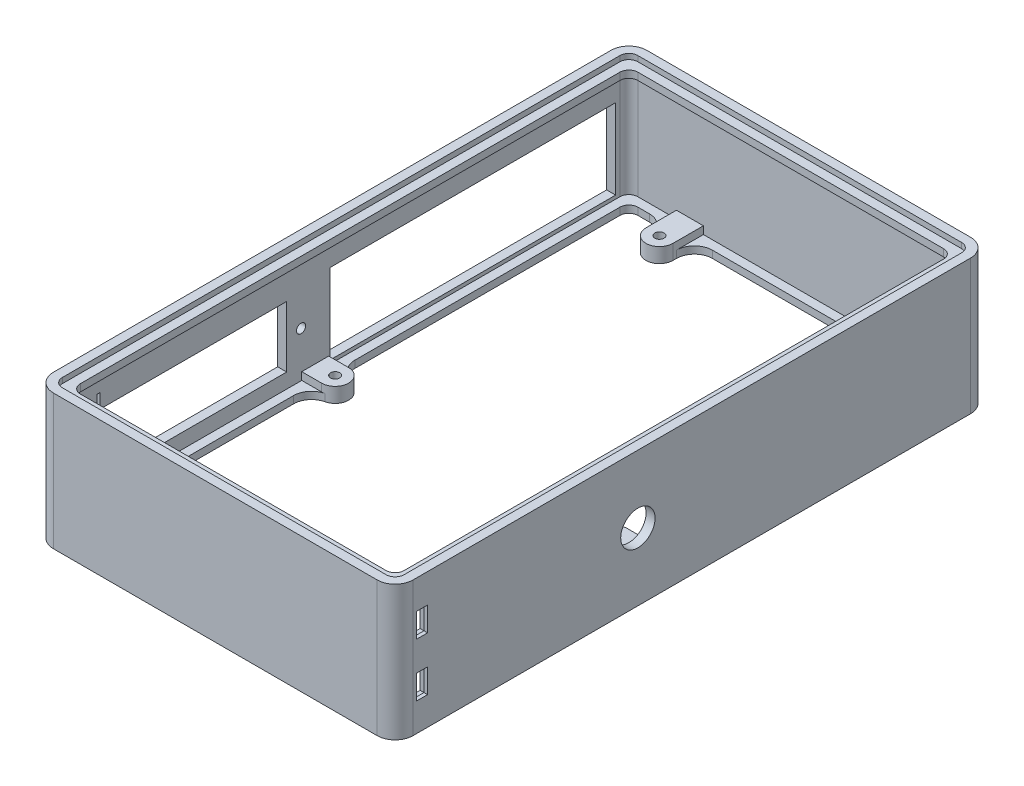
SolidWorks part; units mm, degrees
ref_plane "Front Plane" through (0, 0, 0) normal (0, 0, 1) x (1, 0, 0)
ref_plane "Top Plane" through (0, 0, 0) normal (0, 1, 0) x (1, 0, 0)
ref_plane "Right Plane" through (0, 0, 0) normal (1, 0, 0) x (0, 0, -1)
sketch "Sketch1" plane through (0, 0, 0) normal (0, 1, 0) x (1, 0, 0)
  line L1 (0, 0) -> (200, 0)
  line L2 (0, 0) -> (0, 330)
  line L3 (0, 330) -> (200, 330)
  line L4 (200, 0) -> (200, 330)
extrude "Boss-Extrude1" add sketch "Sketch1" along normal blind 75
fillet "Fillet1" radius 10 4 edges at (0, 37.5, -330) (200, 37.5, -330) (0, 37.5, 0) (200, 37.5, 0)
sketch "Sketch2" plane through (0, 75, 0) normal (0, 1, 0) x (1, 0, 0)
  line L8 (190, 325) -> (10, 325)
  line L9 (5, 320) -> (5, 10)
  line L10 (10, 5) -> (190, 5)
  line L11 (195, 10) -> (195, 320)
  line L12 (190, 325) -> (10, 325)
  line L13 (5, 320) -> (5, 10)
  line L14 (10, 5) -> (190, 5)
  line L15 (195, 10) -> (195, 320)
  arc A8 (10, 325) -> (5, 320) centre (10, 320) ccw
  arc A9 (5, 10) -> (10, 5) centre (10, 10) ccw
  arc A10 (190, 5) -> (195, 10) centre (190, 10) ccw
  arc A11 (195, 320) -> (190, 325) centre (190, 320) ccw
  arc A12 (10, 325) -> (5, 320) centre (10, 320) ccw
  arc A13 (5, 10) -> (10, 5) centre (10, 10) ccw
  arc A14 (190, 5) -> (195, 10) centre (190, 10) ccw
  arc A15 (195, 320) -> (190, 325) centre (190, 320) ccw
  dimension "D1" = 5
extrude "Cut-Extrude1" cut sketch "Sketch2" against normal blind 75
ref_plane "Plane1" through (0, 72, 0) normal (0, 1, 0) x (1, 0, 0)
ref_plane "Plane2" through (0, 3, 0) normal (0, -1, 0) x (-1, 0, 0)
sketch "Sketch3" plane through (0, 72, 0) normal (0, 1, 0) x (1, 0, 0)
  line L0 (10, 5) -> (190, 5) construction
  line L1 (195, 10) -> (195, 320) construction
  line L2 (5, 320) -> (5, 10) construction
  line L3 (190, 325) -> (10, 325) construction
  line L4 (10, 5) -> (190, 5)
  line L5 (195, 10) -> (195, 320)
  line L6 (5, 320) -> (5, 10)
  line L7 (190, 325) -> (10, 325)
  line L8 (10, 10) -> (190, 10)
  line L9 (190, 10) -> (190, 320)
  line L10 (190, 320) -> (10, 320)
  line L11 (10, 320) -> (10, 10)
  arc A0 (5, 10) -> (10, 5) centre (10, 10) ccw construction
  arc A1 (190, 5) -> (195, 10) centre (190, 10) ccw construction
  arc A2 (195, 320) -> (190, 325) centre (190, 320) ccw construction
  arc A3 (10, 325) -> (5, 320) centre (10, 320) ccw construction
  arc A4 (5, 10) -> (10, 5) centre (10, 10) ccw
  arc A5 (190, 5) -> (195, 10) centre (190, 10) ccw
  arc A6 (195, 320) -> (190, 325) centre (190, 320) ccw
  arc A7 (10, 325) -> (5, 320) centre (10, 320) ccw
  arc A8 (10, 10) -> (10, 10) centre (10, 10) ccw
  arc A9 (190, 10) -> (190, 10) centre (190, 10) ccw
  arc A10 (190, 320) -> (190, 320) centre (190, 320) ccw
  arc A11 (10, 320) -> (10, 320) centre (10, 320) ccw
  dimension "D1" = 5
extrude "Boss-Extrude2" add sketch "Sketch3" against normal blind 4
sketch "Sketch4" plane through (0, 3, 0) normal (0, -1, 0) x (-1, 0, 0)
  line L0 (-190, 320) -> (-190, 10)
  line L1 (-190, 10) -> (-10, 10)
  line L2 (-10, 10) -> (-10, 320)
  line L3 (-10, 320) -> (-190, 320)
  line L4 (-5, 10) -> (-5, 320)
  line L5 (-10, 325) -> (-190, 325)
  line L6 (-195, 320) -> (-195, 10)
  line L7 (-190, 5) -> (-10, 5)
  line L8 (-5, 10) -> (-5, 320)
  line L9 (-10, 325) -> (-190, 325)
  line L10 (-195, 320) -> (-195, 10)
  line L11 (-190, 5) -> (-10, 5)
  arc A0 (-190, 10) -> (-190, 10) centre (-190, 10) ccw
  arc A1 (-10, 10) -> (-10, 10) centre (-10, 10) ccw
  arc A2 (-10, 320) -> (-10, 320) centre (-10, 320) ccw
  arc A3 (-190, 320) -> (-190, 320) centre (-190, 320) ccw
  arc A4 (-10, 5) -> (-5, 10) centre (-10, 10) ccw
  arc A5 (-5, 320) -> (-10, 325) centre (-10, 320) ccw
  arc A6 (-190, 325) -> (-195, 320) centre (-190, 320) ccw
  arc A7 (-195, 10) -> (-190, 5) centre (-190, 10) ccw
  arc A8 (-10, 5) -> (-5, 10) centre (-10, 10) ccw
  arc A9 (-5, 320) -> (-10, 325) centre (-10, 320) ccw
  arc A10 (-190, 325) -> (-195, 320) centre (-190, 320) ccw
  arc A11 (-195, 10) -> (-190, 5) centre (-190, 10) ccw
  dimension "D1" = 0
  dimension "D2" = 5
extrude "Boss-Extrude3" add sketch "Sketch4" against normal blind 4
sketch "Sketch8" plane through (5, 0, 0) normal (1, 0, 0) x (0, 0, -1)
  line L0 (320, 7) -> (317.62, 7)
  line L1 (10, 7) -> (320, 7) construction
  line L2 (317.62, 7) -> (317.62, 9)
  line L3 (317.62, 9) -> (317.62, 53.5)
  line L4 (317.62, 53.5) -> (158.87, 53.5)
  line L6 (158.87, 53.5) -> (317.62, 53.5)
  line L7 (158.87, 53.5) -> (158.87, 9)
  line L8 (158.87, 9) -> (317.62, 9)
  line L9 (317.62, 53.5) -> (317.62, 9)
extrude "Cut-Extrude2" cut sketch "Sketch8" against normal blind 40 contours L7 L8 L3 L4 region at (5, 31.25, -238.245)
sketch "Sketch11" plane through (0, 3, 0) normal (0, -1, 0) x (1, 0, 0)
  line L1 (16.06, -158.09) -> (10, -158.09)
  line L2 (10, -10) -> (10, -320) construction
  line L4 (10, -143.09) -> (16.06, -143.09)
  line L5 (31.42, -308.07) -> (31.42, -320)
  line L6 (10, -320) -> (190, -320) construction
  line L8 (46.42, -320) -> (46.42, -308.07)
  line L9 (171, -300.57) -> (190, -300.57)
  line L10 (190, -320) -> (190, -10) construction
  line L13 (163.5, -320) -> (163.5, -308.07)
  line L14 (171, -158.09) -> (190, -158.09)
  line L16 (190, -143.09) -> (171, -143.09)
  line L17 (190, -158.09) -> (195, -158.09)
  line L18 (195, -10) -> (195, -320) construction
  line L19 (195, -158.09) -> (195, -143.09)
  line L20 (195, -320) -> (195, -10) construction
  line L21 (195, -143.09) -> (190, -143.09)
  line L22 (190, -300.57) -> (195, -300.57)
  line L23 (195, -300.57) -> (195, -320)
  line L24 (163.5, -320) -> (163.5, -325)
  line L25 (190, -325) -> (10, -325) construction
  line L26 (163.5, -325) -> (190, -325)
  line L27 (5, -10) -> (5, -320) construction
  line L29 (46.42, -320) -> (46.42, -325)
  line L30 (46.42, -325) -> (31.42, -325)
  line L31 (31.42, -320) -> (31.42, -325)
  line L32 (10, -158.09) -> (5, -158.09)
  line L34 (10, -143.09) -> (5, -143.09)
  line L35 (5, -158.09) -> (5, -143.09)
  circle A0 centre (38.92, -308.07) radius 2.55
  circle A1 centre (171, -308.07) radius 2.55
  circle A2 centre (171, -150.59) radius 2.55
  circle A3 centre (16.06, -150.59) radius 2.55
  arc A4 (16.06, -158.09) -> (16.06, -143.09) centre (16.06, -150.59) ccw
  arc A5 (171, -143.09) -> (171, -158.09) centre (171, -150.59) ccw
  arc A6 (171, -300.57) -> (163.5, -308.07) centre (171, -308.07) ccw
  arc A7 (46.42, -308.07) -> (31.42, -308.07) centre (38.92, -308.07) ccw
  arc A8 (190, -325) -> (195, -320) centre (190, -320) ccw construction
  arc A9 (190, -325) -> (195, -320) centre (190, -320) ccw
extrude "Boss-Extrude4" add sketch "Sketch11" against normal blind 8.23
sketch "Sketch12" plane through (0, 0, 0) normal (-1, 0, 0) x (0, 0, 1)
  line L0 (-134.7, 32.25) -> (-142.7, 32.25)
  line L4 (-134.7, 15.25) -> (-32.9, 15.25)
  line L5 (-134.7, 15.25) -> (-134.7, 49.25)
  line L6 (-134.7, 49.25) -> (-32.9, 49.25)
  line L7 (-32.9, 49.25) -> (-32.9, 15.25)
  circle A0 centre (-142.7, 32.25) radius 2.55
extrude "Cut-Extrude3" cut sketch "Sketch12" against normal blind 31.23 contours L7 L6 L5 L4 | A0 region at (0, 32.25, -145.1779) region at (0, 32.25, -83.8)
sketch "Sketch13" plane through (195, 0, 0) normal (-1, 0, 0) x (0, 0, 1)
  line L0 (-10, 37.5) -> (-130, 37.5)
  line L1 (-10, 7) -> (-10, 68) construction
  line L2 (-10, 37.5) -> (-135, 37.5)
  circle A0 centre (-135, 37.5) radius 9.55
extrude "Cut-Extrude4" cut sketch "Sketch13" against normal blind 31.23
fillet "Fillet2" radius 10 4 edges at (31.42, 5, -320) (46.42, 5, -320) (10, 5, -143.09) (10, 5, -158.09)
fillet "Fillet3" radius 20 2 edges at (190, 5, -143.09) (190, 5, -158.09)
fillet "Fillet4" radius 5 7 edges at (10, 5, -10) (190, 5, -10) (10, 5, -320) (10, 70, -320) (190, 70, -320) (190, 70, -10) (10, 70, -10)
sketch "Sketch14" plane through (0, 0, 0) normal (-1, 0, 0) x (0, 0, 1)
  line L0 (-32.9, 15.25) -> (-30.9, 15.25)
  line L1 (-30.9, 15.25) -> (-30.9, 10.25)
  line L2 (-30.9, 10.25) -> (-29.15, 10.25)
  line L3 (-32.9, 49.25) -> (-30.9, 49.25)
  line L4 (-30.9, 49.25) -> (-30.9, 57.25)
  line L6 (-30.9, 57.25) -> (-29.15, 57.25)
  line L7 (-30.9, 57.25) -> (-30.9, 10.25)
  line L8 (-30.9, 10.25) -> (-29.15, 10.25)
  line L9 (-29.15, 57.25) -> (-29.15, 10.25)
extrude "Cut-Extrude5" cut sketch "Sketch14" against normal blind 10 contours L9 L6 L4 L7 L1 L2 region at (0, 33.75, -30.025)
sketch "Sketch15" plane through (0, 0, 0) normal (-1, 0, 0) x (0, 0, 1)
  line L1 (-30.9, 10.25) -> (-32.9, 10.25)
  line L2 (-30.9, 10.25) -> (-30.9, 57.2714)
  line L3 (-30.9, 57.2714) -> (-32.9, 57.2714)
  line L4 (-32.9, 10.25) -> (-32.9, 57.2714)
extrude "Boss-Extrude5" add sketch "Sketch15" along normal blind 8
sketch "Sketch16" plane through (0, 0, -32.9) normal (0, 0, -1) x (-1, 0, 0)
  line L0 (0, 15.25) -> (0.5, 15.25)
  line L1 (0.5, 15.25) -> (0.5, 31.75)
  circle A0 centre (0.5, 31.75) radius 2.55
extrude "Cut-Extrude6" cut sketch "Sketch16" against normal blind 2 contours A0 region at (-2.2521, 29.9979, -32.9)
sketch "Sketch17" plane through (0, 0, -32.9) normal (0, 0, -1) x (-1, 0, 0)
  circle A0 centre (0.5, 31.75) radius 4.5
  circle A1 centre (0.5, 31.75) radius 2.55
extrude "Boss-Extrude6" add sketch "Sketch17" along normal blind 3
chamfer "Chamfer1" distance 3 angle 45 1 edges at (-5, 31.75, -32.9)
fillet "Fillet5" radius 5 2 edges at (-8, 57.2714, -31.9) (-8, 10.25, -31.9)
chamfer "Chamfer2" distance 3 angle 45 2 edges at (0, 53.2607, -32.9) (0, 12.75, -32.9)
sketch "Sketch19" plane through (200, 0, 0) normal (1, 0, 0) x (0, 0, -1)
  line L0 (5, 7) -> (5, 68) construction
  line L1 (5, 7) -> (5, 68)
  line L2 (5, 37.5) -> (25, 37.5)
  line L3 (15, 37.5) -> (15, 52)
  line L4 (15, 52) -> (15, 22.25)
  line L5 (15, 52) -> (15, 44.75)
  line L6 (15, 44.75) -> (18.5, 44.75)
  line L7 (15, 22.25) -> (15, 29.5)
  line L8 (18.5, 44.75) -> (11.5, 44.75)
  line L9 (18.5, 44.75) -> (18.5, 59.25)
  line L10 (18.5, 59.25) -> (11.5, 59.25)
  line L11 (11.5, 44.75) -> (11.5, 59.25)
  line L12 (15, 29.5) -> (18.5, 29.5)
  line L14 (18.5, 29.5) -> (11.5, 29.5)
  line L15 (18.5, 29.5) -> (18.5, 15)
  line L16 (18.5, 15) -> (11.5, 15)
  line L17 (11.5, 29.5) -> (11.5, 15)
extrude "Cut-Extrude8" cut sketch "Sketch19" against normal blind 18 contours L11 L8 L6 L9 L10 | L14 L17 L16 L15 L12 region at (200, 44.911, -13.25) region at (200, 29.339, -16.75)
sketch "Sketch20" plane through (0, 0, -5) normal (0, 0, -1) x (-1, 0, 0)
  line L0 (-195, 29.5) -> (-195, 15) construction
  line L1 (-195, 29.5) -> (-195, 15)
  line L2 (-195, 20.2001) -> (-188, 20.2001)
  line L3 (-188, 20.2001) -> (-185, 20.2001)
  line L4 (-195, 44.75) -> (-195, 59.25) construction
  line L5 (-195, 44.75) -> (-195, 59.25)
  line L6 (-195, 29.5) -> (-195, 15)
  line L7 (-195, 29.5) -> (-195, 44.75)
  line L8 (-195, 15) -> (-185, 15)
  line L9 (-185, 37.125) -> (-185, 62.125)
  line L10 (-180, 37.125) -> (-178, 37.125)
  line L11 (-185, 37.125) -> (-185, 12.125)
  line L12 (-185, 12.125) -> (-170, 12.125)
  line L13 (-185, 59.25) -> (-170, 59.25)
  line L14 (-185, 62.125) -> (-170, 62.125)
  circle A0 centre (-178, 37.125) radius 2.55
  circle A1 centre (-168, 62.125) radius 2.55
  circle A2 centre (-168, 12.125) radius 2.55
sketch "Sketch22" plane through (200, 0, 0) normal (1, 0, 0) x (0, 0, -1)
  line L0 (11.5, 44.75) -> (11.5, 59.25) construction
  line L1 (18.5, 59.25) -> (11.5, 59.25)
  line L2 (18.5, 59.25) -> (18.5, 59.625)
  line L3 (18.5, 59.625) -> (11.5, 59.625)
  line L4 (11.5, 59.25) -> (11.5, 59.625)
  line L5 (11.5, 29.5) -> (11.5, 15) construction
  line L6 (18.5, 29.5) -> (11.5, 29.5)
  line L7 (18.5, 29.5) -> (18.5, 29.875)
  line L8 (18.5, 29.875) -> (11.5, 29.875)
  line L9 (11.5, 29.5) -> (11.5, 29.875)
extrude "Cut-Extrude9" cut sketch "Sketch22" against normal blind 18
sketch "Sketch23" plane through (200, 0, 0) normal (1, 0, 0) x (0, 0, -1)
  line L0 (11.5, 44.75) -> (11.5, 59.625) construction
  line L1 (18.5, 44.75) -> (11.5, 44.75)
  line L2 (18.5, 44.75) -> (18.5, 45.125)
  line L3 (18.5, 45.125) -> (11.5, 45.125)
  line L4 (11.5, 44.75) -> (11.5, 45.125)
  line L5 (11.5, 29.875) -> (11.5, 15) construction
  line L6 (18.5, 15) -> (11.5, 15)
  line L7 (18.5, 15) -> (18.5, 15.375)
  line L8 (18.5, 15.375) -> (11.5, 15.375)
  line L9 (11.5, 15) -> (11.5, 15.375)
extrude "Boss-Extrude7" add sketch "Sketch23" against normal up to surface (5 mm away) up to face at (195, 52.1875, -15)
extrude "Cut-Extrude10" cut sketch "Sketch20" against normal blind 18 contours A2 | A0 | A1 region at (168, 12.125, -5)
sketch "Sketch24" plane through (200, 0, 0) normal (1, 0, 0) x (0, 0, -1)
  line L23 (11, 14.875) -> (19, 14.875)
  line L24 (11, 30.375) -> (11, 14.875)
  line L25 (19, 30.375) -> (11, 30.375)
  line L26 (19, 14.875) -> (19, 30.375)
  line L27 (11, 14.875) -> (19, 14.875)
  line L28 (11, 30.375) -> (11, 14.875)
  line L29 (19, 30.375) -> (11, 30.375)
  line L30 (19, 14.875) -> (19, 30.375)
  line L143 (19, 44.625) -> (19, 60.125)
  line L144 (11, 44.625) -> (19, 44.625)
  line L145 (11, 60.125) -> (11, 44.625)
  line L146 (19, 60.125) -> (11, 60.125)
  line L147 (19, 44.625) -> (19, 60.125)
  line L148 (11, 44.625) -> (19, 44.625)
  line L149 (11, 60.125) -> (11, 44.625)
  line L150 (19, 60.125) -> (11, 60.125)
  dimension "D1" = 0.5
  dimension "D2" = 0.5
extrude "Cut-Extrude12" cut sketch "Sketch24" against normal blind 10
sketch "Sketch25" plane through (200, 0, 0) normal (1, 0, 0) x (0, 0, -1)
  line L0 (11, 60.125) -> (11, 44.625) construction
  line L1 (19, 60.125) -> (11, 60.125)
  line L2 (19, 60.125) -> (19, 59.725)
  line L3 (19, 59.725) -> (11, 59.725)
  line L4 (11, 60.125) -> (11, 59.725)
  line L6 (19, 30.375) -> (11, 30.375)
  line L7 (19, 30.375) -> (19, 29.975)
  line L8 (19, 29.975) -> (11, 29.975)
  line L9 (11, 30.375) -> (11, 29.975)
extrude "Boss-Extrude8" add sketch "Sketch25" against normal up to surface (5 mm away) up to face at (195, 1.5, -165)
sketch "Sketch26" plane through (200, 0, 0) normal (1, 0, 0) x (0, 0, -1)
  line L1 (11, 44.625) -> (11.1, 44.625)
  line L2 (11, 44.625) -> (11, 59.725)
  line L3 (11, 59.725) -> (11.1, 59.725)
  line L4 (11.1, 44.625) -> (11.1, 59.725)
  line L9 (19, 44.625) -> (18.9, 44.625)
  line L10 (19, 44.625) -> (19, 59.725)
  line L11 (19, 59.725) -> (18.9, 59.725)
  line L12 (18.9, 44.625) -> (18.9, 59.725)
  line L17 (19, 29.975) -> (18.9, 29.975)
  line L18 (19, 29.975) -> (19, 14.875)
  line L19 (19, 14.875) -> (18.9, 14.875)
  line L20 (18.9, 29.975) -> (18.9, 14.875)
  line L25 (11, 14.875) -> (11.1, 14.875)
  line L26 (11, 14.875) -> (11, 29.975)
  line L27 (11, 29.975) -> (11.1, 29.975)
  line L28 (11.1, 14.875) -> (11.1, 29.975)
extrude "Boss-Extrude9" add sketch "Sketch26" against normal up to surface (5 mm away) up to face at (195, 1.5, -165)
sketch "Sketch27" plane through (200, 0, 0) normal (1, 0, 0) x (0, 0, -1)
  line L0 (18.9, 52.175) -> (11.1, 52.175)
  line L1 (18.9, 59.725) -> (18.9, 44.625) construction
  line L2 (11.1, 44.625) -> (11.1, 59.725) construction
  line L3 (11.1, 52.175) -> (15, 52.175)
  line L4 (15, 52.175) -> (15, 58.875)
  line L5 (15, 58.875) -> (18.05, 58.875)
  line L6 (18.9, 22.425) -> (11.1, 22.425)
  line L7 (18.05, 58.875) -> (11.95, 58.875)
  line L8 (18.05, 58.875) -> (18.05, 45.475)
  line L9 (18.05, 45.475) -> (11.95, 45.475)
  line L10 (11.95, 58.875) -> (11.95, 45.475)
  line L11 (18.9, 59.725) -> (11.1, 59.725)
  line L12 (18.9, 59.725) -> (18.9, 44.625)
  line L13 (18.9, 44.625) -> (11.1, 44.625)
  line L14 (11.1, 59.725) -> (11.1, 44.625)
  line L15 (18.9, 29.975) -> (18.9, 14.875) construction
  line L16 (11.1, 14.875) -> (11.1, 29.975) construction
  line L17 (11.1, 22.425) -> (15, 22.425)
  line L18 (15, 22.425) -> (15, 29.125)
  line L19 (15, 29.125) -> (18.05, 29.125)
  line L21 (18.05, 29.125) -> (11.95, 29.125)
  line L22 (18.05, 29.125) -> (18.05, 15.725)
  line L23 (18.05, 15.725) -> (11.95, 15.725)
  line L24 (11.95, 29.125) -> (11.95, 15.725)
  line L25 (18.9, 29.975) -> (11.1, 29.975)
  line L26 (18.9, 29.975) -> (18.9, 14.875)
  line L27 (18.9, 14.875) -> (11.1, 14.875)
  line L28 (11.1, 29.975) -> (11.1, 14.875)
  line M5 (18.9, 14.875) -> (11.1, 14.875)
  line M6 (11.1, 14.875) -> (11.1, 29.975)
  line M7 (11.1, 29.975) -> (18.9, 29.975)
  line M8 (18.9, 29.975) -> (18.9, 14.875)
  line M9 (18.9, 44.625) -> (11.1, 44.625)
  line M10 (11.1, 44.625) -> (11.1, 59.725)
  line M11 (11.1, 59.725) -> (18.9, 59.725)
  line M12 (18.9, 59.725) -> (18.9, 44.625)
extrude "Boss-Extrude10" add sketch "Sketch27" against normal blind 2 contours L24 L21 L19 L22 L6 L17 M8 M7 M6 | L24 L17 L6 L22 L23 M6 M5 M8 | L10 L3 L0 L8 L9 M10 M9 M12 | L10 L7 L5 L8 L0 L3 M12 M11 M10 region at (200, 48.4, -18.7914) region at (200, 52.2836, -18.475) region at (200, 18.65, -18.7914) region at (200, 22.5336, -18.475)
sketch "Sketch28" plane through (0, 0, -5) normal (0, 0, -1) x (-1, 0, 0)
  line L1 (-183.2614, 41.5619) -> (-170.2756, 41.5619)
  line L2 (-183.2614, 41.5619) -> (-183.2614, 31.146)
  line L3 (-183.2614, 31.146) -> (-170.2756, 31.146)
  line L4 (-170.2756, 41.5619) -> (-170.2756, 31.146)
extrude "Boss-Extrude11" add sketch "Sketch28" against normal up to surface (5 mm away) up to face at (165.45, 12.125, 0)
sketch "Sketch29" plane through (0, 0, 0) normal (0, 0, 1) x (1, 0, 0)
  circle A0 centre (168, 62.125) radius 2.55
  circle A1 centre (168, 12.125) radius 2.55
extrude "Boss-Extrude12" add sketch "Sketch29" against normal blind 0.6
